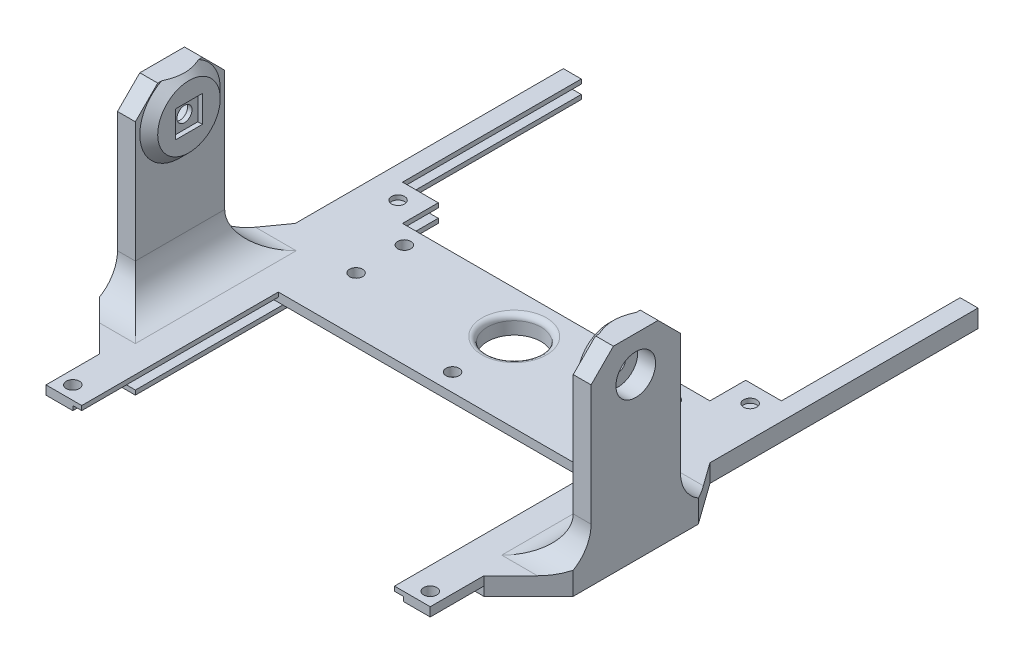
SolidWorks part; units mm, degrees
ref_plane "Alzado" through (0, 0, 0) normal (0, 0, 1) x (1, 0, 0)
ref_plane "Planta" through (0, 0, 0) normal (0, 1, 0) x (1, 0, 0)
ref_plane "Vista lateral" through (0, 0, 0) normal (1, 0, 0) x (0, 0, -1)
sketch "Croquis1" plane through (0, 0, 0) normal (0, 1, 0) x (1, 0, 0)
  line L0 (116, 58) -> (132.5, 35)
  line L8 (116, 88) -> (116, 58)
  line L12 (-132.5, 35) -> (-132.5, -35)
  line L18 (-107.5, -60) -> (-132.5, -35)
  line L22 (-116, 88) -> (-116, 58)
  line L23 (-116, 58) -> (-132.5, 35)
  line L552 (107.5, -60) -> (132.5, -35)
  line L553 (132.5, 35) -> (132.5, -35)
  line L554 (0, 0) -> (0, -155) construction
  line L558 (-80, -60) -> (0, -60) construction
  line L559 (0, -60) -> (80, -60) construction
  line L566 (-132.5, 0) -> (0, 0) construction
  line L567 (0, 0) -> (132.5, 0) construction
  line L569 (0, 101) -> (0, 0) construction
  line L570 (-116, 88) -> (116, 88)
  line L572 (-92.5, -90) -> (-92.5, 40)
  line L573 (-92.5, 40) -> (92.5, 40)
  line L574 (92.5, 40) -> (92.5, -90)
  line L577 (-107.5, -60) -> (-107.5, -90)
  line L578 (-107.5, -90) -> (-92.5, -90)
  line L579 (107.5, -60) -> (107.5, -90)
  line L580 (107.5, -90) -> (92.5, -90)
  point P12 (0, 0)
  point P16 (-132.5, 0)
  point P18 (0, 0)
  dimension "D8" = 25
  dimension "D2" = 232
  dimension "D4" = 30
  dimension "D5" = 30
  dimension "D6" = 130
  dimension "D7" = 23
  dimension "D9" = 25
  dimension "D10" = 15
  dimension "D16" = 265
  dimension "D30" = 70
extrude "Saliente-Extruir2" add sketch "Croquis1" along normal blind 10
sketch "Croquis3" plane through (0, 10, 0) normal (0, 1, 0) x (1, 0, 0)
  line L0 (132.5, 25) -> (122.5, 25)
  line L1 (132.5, -35) -> (132.5, 35) construction
  line L2 (122.5, 25) -> (122.5, -25)
  line L3 (122.5, -25) -> (132.5, -25)
  line L4 (132.5, -25) -> (132.5, 25)
  line L5 (132.5, 35) -> (132.5, 25) construction
  line L6 (132.5, -25) -> (132.5, -35) construction
  line L7 (0, -155) -> (0, -12.7186) construction
  line L10 (0, -135.114) -> (0, 15) construction
  line L11 (0, 64.5) -> (0, -38.3443) construction
  line L12 (-122.5, -25) -> (-132.5, -25)
  line L13 (-122.5, 25) -> (-122.5, -25)
  line L14 (-132.5, 25) -> (-122.5, 25)
  line L15 (-132.5, -25) -> (-132.5, 25)
  point P13 (0, 0)
  point P25 (0, 0)
  dimension "D1" = 10
  dimension "D2" = 50
extrude "Saliente-Extruir4" add sketch "Croquis3" along normal blind 100
sketch "Croquis4" plane through (132.5, 0, 0) normal (1, 0, 0) x (0, 0, -1)
  line L0 (0, 110) -> (0, 90) construction
  line L1 (-25, 110) -> (25, 110) construction
  circle A0 centre (0, 90) radius 11.1
  dimension "D1" = 22.2
  dimension "D2" = 20
extrude "Cortar-Extruir1" cut sketch "Croquis4" against normal through all both and the other way through all
sketch "Croquis5" plane through (122.5, 0, 0) normal (-1, 0, 0) x (0, 0, 1)
  circle A0 centre (0, 90) radius 17.5
  circle A1 centre (0, 90) radius 4.2
  dimension "D1" = 8.4
  dimension "D2" = 35
extrude "Saliente-Extruir5" add sketch "Croquis5" along normal blind 5
chamfer "Chaflán1" distance 5 angle 45 1 edges at (122.5, 90, -17.5)
sketch "Croquis6" plane through (-122.5, 0, 0) normal (1, 0, 0) x (0, 0, -1)
  circle A0 centre (0, 90) radius 4.2
  circle A1 centre (0, 90) radius 17.5
  dimension "D1" = 35
  dimension "D2" = 8.4
extrude "Saliente-Extruir6" add sketch "Croquis6" along normal blind 5
chamfer "Chaflán3" distance 12.5 angle 45 4 edges at (-127.5, 110, -25) (-127.5, 110, 25) (127.5, 110, -25) (127.5, 110, 25)
chamfer "Chaflán2" distance 5 angle 45 1 edges at (-122.5, 90, 17.5)
sketch "Croquis8" plane through (-117.5, 0, 0) normal (1, 0, 0) x (0, 0, -1)
  line L1 (-7.5, 97.5) -> (7.5, 97.5)
  line L2 (-7.5, 97.5) -> (-7.5, 82.5)
  line L3 (-7.5, 82.5) -> (7.5, 82.5)
  line L4 (7.5, 97.5) -> (7.5, 82.5)
  line L5 (-7.5, 97.5) -> (7.5, 82.5) construction
  line L6 (-7.5, 82.5) -> (7.5, 97.5) construction
  circle A0 centre (0, 90) radius 4.2
  dimension "D2" = 8.4
  dimension "D1" = 15
extrude "Cortar-Extruir3" cut sketch "Croquis8" against normal blind 2.5
fillet "Redondeo1" radius 20 6 edges at (-127.5, 10, -25) (-127.5, 10, 25) (-122.5, 10, 0) (122.5, 10, 0) (127.5, 10, -25) (127.5, 10, 25)
sketch "Croquis14" plane through (0, 0, -88) normal (0, 0, -1) x (-1, 0, 0)
  line L0 (-86, 10) -> (-116, 10)
  line L1 (-116, 10) -> (-116, 0)
  line L2 (-116, 0) -> (-86, 0)
  line L3 (-116, 0) -> (116, 0) construction
  line L4 (-86, 0) -> (-86, 2.5)
  line L5 (-86, 2.5) -> (-111, 2.5)
  line L6 (-111, 2.5) -> (-111, 7.5)
  line L7 (-111, 7.5) -> (-86, 7.5)
  line L8 (-86, 7.5) -> (-86, 10)
  line L9 (0, 0) -> (0, 10) construction
  line L10 (-116, 10) -> (116, 10) construction
  line L11 (111, 7.5) -> (86, 7.5)
  line L12 (111, 2.5) -> (111, 7.5)
  line L13 (86, 2.5) -> (111, 2.5)
  line L14 (86, 0) -> (86, 2.5)
  line L15 (116, 0) -> (86, 0)
  line L16 (116, 10) -> (116, 0)
  line L17 (86, 10) -> (116, 10)
  line L18 (86, 7.5) -> (86, 10)
  dimension "D1" = 30
  dimension "D2" = 5
  dimension "D3" = 2.5
extrude "Saliente-Extruir9" add sketch "Croquis14" along normal blind 20
sketch "Croquis7" plane through (117.5, 0, 0) normal (-1, 0, 0) x (0, 0, 1)
  line L1 (-7.5, 97.5) -> (7.5, 97.5)
  line L2 (-7.5, 97.5) -> (-7.5, 82.5)
  line L3 (-7.5, 82.5) -> (7.5, 82.5)
  line L4 (7.5, 97.5) -> (7.5, 82.5)
  line L5 (-7.5, 97.5) -> (7.5, 82.5) construction
  line L6 (-7.5, 82.5) -> (7.5, 97.5) construction
  circle A0 centre (0, 90) radius 4.2
  dimension "D2" = 8.4
  dimension "D1" = 15
extrude "Cortar-Extruir2" cut sketch "Croquis7" against normal blind 2.5
sketch "Croquis9" plane through (0, 10, 0) normal (0, 1, 0) x (1, 0, 0)
  line L0 (0, 0) -> (0, 64.5) construction
  line L1 (0, 64.5) -> (0, 88) construction
  line L2 (86, 88) -> (-86, 88) construction
  line L3 (0, 78) -> (-75, 78) construction
  line L4 (-75, 78) -> (-75, 88) construction
  line L5 (0, 64.5) -> (-49.1848, 64.5) construction
  line L6 (100, -90) -> (100, -75) construction
  line L7 (92.5, -90) -> (107.5, -90) construction
  line L8 (86, 98) -> (111, 98) construction
  line L9 (86, 108) -> (86, 88) construction
  circle A0 centre (0, 64.5) radius 15
  circle A1 centre (-75, 78) radius 3.65
  circle A2 centre (75, 78) radius 3.65
  circle A3 centre (75, 51) radius 3.65
  circle A4 centre (-75, 51) radius 3.65
  circle A5 centre (100, -82.5) radius 3.65
  circle A6 centre (-100, -82.5) radius 3.65
  circle A7 centre (98.5, 98) radius 3.65
  circle A8 centre (-98.5, 98) radius 3.65
  dimension "D3" = 30
  dimension "D6" = 7.3
  dimension "D8" = 7.3
  dimension "D10" = 7.3
  dimension "D1" = 64.5
  dimension "D2" = 23.5
  dimension "D4" = 13.5
  dimension "D5" = 75
  dimension "D7" = 15
  dimension "D9" = 25
extrude "Cortar-Extruir4" cut sketch "Croquis9" against normal blind 10
fillet "Redondeo2" radius 3 1 edges at (0, 10, -49.5)
sketch "Croquis11" plane through (0, 10, 0) normal (0, 1, 0) x (1, 0, 0)
  line L1 (-92.5, 40) -> (92.5, 40)
  line L8 (-92.5, 40) -> (-92.5, 20)
  line L9 (-92.5, -90) -> (-92.5, 40) construction
  line L10 (-92.5, 20) -> (92.5, 20)
  line L11 (92.5, 40) -> (92.5, -90) construction
  line L12 (92.5, 20) -> (92.5, 40)
  line L13 (0, 20) -> (0, 40) construction
  circle A0 centre (0, 30) radius 3.65
  dimension "D2" = 7.3
  dimension "D1" = 20
extrude "Saliente-Extruir7" add sketch "Croquis11" against normal blind 5
sketch "Croquis12" plane through (0, 0, 90) normal (0, 0, 1) x (1, 0, 0)
  line L0 (-92.5, 10) -> (-87.5, 10)
  line L1 (-92.5, 10) -> (92.5, 10) construction
  line L2 (-87.5, 10) -> (-87.5, 7.5)
  line L3 (-87.5, 7.5) -> (-92.5, 7.5)
  line L4 (-92.5, 5) -> (-92.5, 10) construction
  line L5 (-92.5, 7.5) -> (-92.5, 5) construction
  line L6 (-92.5, 10) -> (-92.5, 0) construction
  line L7 (-92.5, 2.5) -> (-87.5, 2.5)
  line L8 (-87.5, 2.5) -> (-87.5, 0)
  line L9 (-92.5, 0) -> (92.5, 0) construction
  line L10 (-87.5, 0) -> (-92.5, 0)
  line L11 (-92.5, 0) -> (-92.5, 2.5)
  line L12 (-92.5, 5) -> (-92.5, 2.5) construction
  line L13 (-92.5, 10) -> (-92.5, 7.5)
  line L14 (0, 0) -> (0, 23.8317) construction
  line L15 (92.5, 0) -> (92.5, 2.5)
  line L16 (87.5, 0) -> (92.5, 0)
  line L17 (87.5, 2.5) -> (87.5, 0)
  line L18 (92.5, 2.5) -> (87.5, 2.5)
  line L19 (92.5, 10) -> (87.5, 10)
  line L20 (87.5, 10) -> (87.5, 7.5)
  line L21 (87.5, 7.5) -> (92.5, 7.5)
  line L22 (92.5, 10) -> (92.5, 7.5)
  dimension "D1" = 2.5
  dimension "D2" = 5
extrude "Saliente-Extruir8" add sketch "Croquis12" against normal up to surface (130 mm away) up to face at (0, 2.5, -40)
sketch "Croquis13" plane through (0, 0, 90) normal (0, 0, 1) x (1, 0, 0)
  line L0 (-92.5, 5) -> (-107.5, 5)
  line L1 (-92.5, 7.5) -> (-92.5, 2.5) construction
  line L2 (-107.5, 10) -> (-107.5, 0) construction
  line L3 (-107.5, 5) -> (-107.5, 0)
  line L4 (-107.5, 0) -> (-87.5, 0)
  line L5 (-87.5, 0) -> (-87.5, 5)
  line L6 (-92.5, 5) -> (92.5, 5) construction
  line L7 (-87.5, 5) -> (-92.5, 5)
  line L8 (0, 0) -> (0, 28.3473) construction
  line L9 (87.5, 0) -> (87.5, 5)
  line L10 (107.5, 0) -> (87.5, 0)
  line L11 (107.5, 5) -> (107.5, 0)
  line L12 (92.5, 5) -> (107.5, 5)
  line L13 (87.5, 5) -> (92.5, 5)
extrude "Cortar-Extruir5" cut sketch "Croquis13" against normal blind 30
sketch "Croquis15" plane through (0, 0, -108) normal (0, 0, -1) x (-1, 0, 0)
  line L0 (-106, 2.5) -> (-111, 2.5)
  line L1 (-86, 2.5) -> (-111, 2.5) construction
  line L2 (-111, 2.5) -> (-111, 7.5)
  line L3 (-111, 7.5) -> (-106, 7.5)
  line L4 (-111, 7.5) -> (-86, 7.5) construction
  line L5 (-106, 7.5) -> (-106, 10)
  line L6 (-86, 10) -> (-116, 10) construction
  line L7 (-106, 10) -> (-116, 10)
  line L8 (-116, 10) -> (-116, 0)
  line L9 (-116, 0) -> (-106, 0)
  line L10 (-116, 0) -> (-86, 0) construction
  line L11 (-106, 0) -> (-106, 2.5)
  line L12 (0, 0) -> (0, 6.7597) construction
  line L13 (116, 0) -> (106, 0)
  line L14 (116, 10) -> (116, 0)
  line L15 (106, 10) -> (116, 10)
  line L16 (106, 7.5) -> (106, 10)
  line L17 (111, 7.5) -> (106, 7.5)
  line L18 (111, 2.5) -> (111, 7.5)
  line L19 (106, 2.5) -> (111, 2.5)
  line L20 (106, 0) -> (106, 2.5)
  dimension "D1" = 5
  dimension "D2" = 5
extrude "Saliente-Extruir10" add sketch "Croquis15" along normal blind 100
